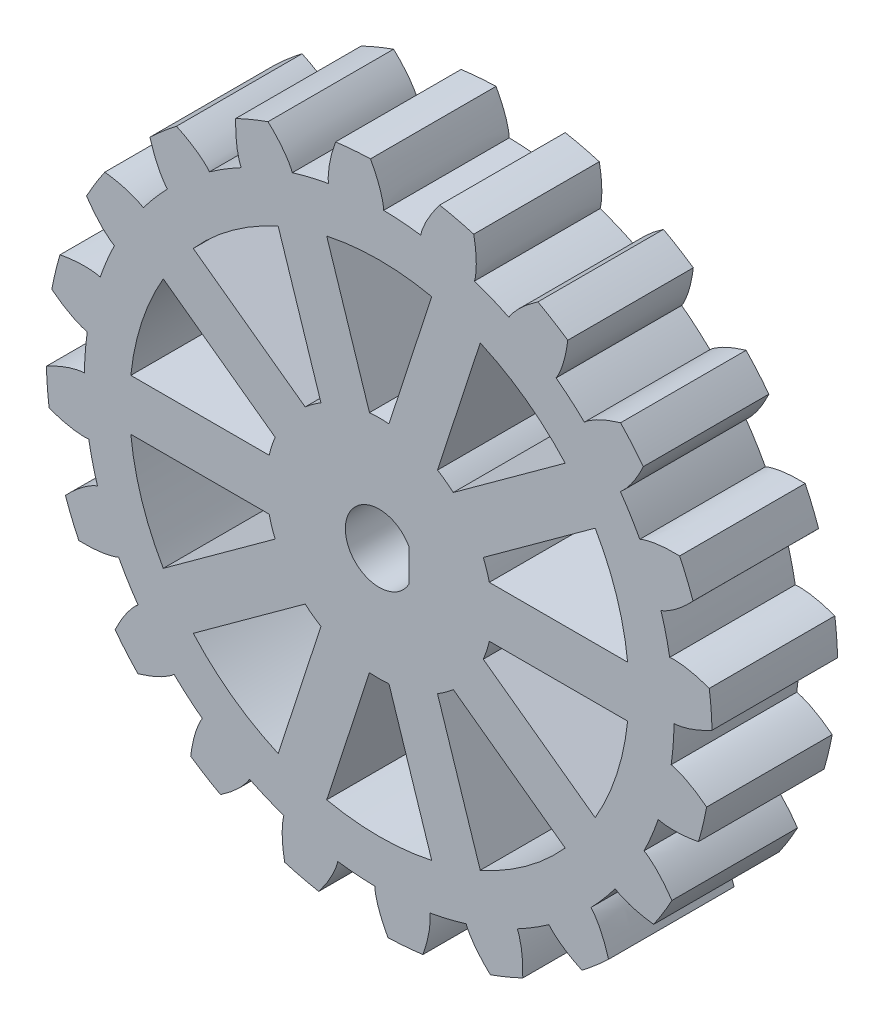
SolidWorks part; units mm, degrees
ref_plane "Front Plane" through (0, 0, 0) normal (0, 0, 1) x (1, 0, 0)
ref_plane "Top Plane" through (0, 0, 0) normal (0, 1, 0) x (1, 0, 0)
ref_plane "Right Plane" through (0, 0, 0) normal (1, 0, 0) x (0, 0, -1)
sketch "Sketch6" plane through (0, 0, 0) normal (0, 0, 1) x (1, 0, 0)
  line L0 (87.6899, 36.827) -> (87.6899, 90.4407) construction
  line L1 (87.6899, 61.8261) -> (62.7181, 61.8261) construction
  line L2 (87.6899, 61.8261) -> (56.3004, 50.4013) construction
  line L3 (79.6554, 58.9018) -> (87.6899, 61.8261) construction
  line L4 (77.8074, 58.1386) -> (87.3788, 62.5771) construction
  line L5 (76.0304, 57.2208) -> (86.9259, 63.45) construction
  line L6 (74.338, 56.1551) -> (86.3097, 64.4252) construction
  line L7 (81.5622, 59.5052) -> (87.8859, 61.2139) construction
  line L8 (83.5134, 59.9442) -> (87.9914, 60.7533) construction
  line L9 (85.4949, 60.2157) -> (88.0342, 60.454) construction
  line L10 (87.4923, 60.3177) -> (88.0428, 60.3223) construction
  line L11 (88.0428, 60.3223) -> (88.0425, 60.3158) construction
  line L12 (88.0425, 60.3158) -> (88.0425, 60.3094) construction
  line L13 (87.6899, 36.827) -> (85.2614, 67.5128) construction
  line L14 (111.173, 36.827) -> (112.6899, 36.827) construction
  line L15 (112.6899, 36.827) -> (114.2068, 36.827) construction
  circle A0 centre (87.6899, 36.827) radius 26.5169 construction
  circle A1 centre (87.6899, 36.827) radius 25 construction
  circle A2 centre (87.6899, 36.827) radius 23.4915 construction
  arc A3 (79.6554, 58.9018) -> (77.8074, 58.1386) centre (87.6899, 36.827) ccw construction
  arc A4 (77.8074, 58.1386) -> (76.0304, 57.2208) centre (87.6899, 36.827) ccw construction
  arc A5 (76.0304, 57.2208) -> (74.338, 56.1551) centre (87.6899, 36.827) ccw construction
  arc A6 (79.6554, 58.9018) -> (81.5622, 59.5052) centre (87.6899, 36.827) cw construction
  arc A7 (81.5622, 59.5052) -> (83.5134, 59.9442) centre (87.6899, 36.827) cw construction
  arc A8 (83.5134, 59.9442) -> (85.4949, 60.2157) centre (87.6899, 36.827) cw construction
  arc A9 (85.4949, 60.2157) -> (87.4923, 60.3177) centre (87.6899, 36.827) cw construction
  circle A10 centre (87.6899, 36.827) radius 23.485 construction
  spline S0 degree 3 poles (88.0425, 60.3094) (88.0393, 60.4586) (87.9965, 60.763) (87.8787, 61.2705) (87.6796, 61.8825) (87.2187, 62.9893) (86.7132, 63.8389) (86.3097, 64.4252) knots 0 0 0 0 0.099096 0.20382 0.346132 0.526411 1 1 1 1 construction
  spline S1 degree 3 poles (83.648, 59.9616) (83.6277, 60.1095) (83.6221, 60.4168) (83.6586, 60.9366) (83.759, 61.5723) (84.04, 62.7378) (84.4056, 63.6562) (84.7119, 64.2988) knots 0 0 0 0 0.099096 0.20382 0.346132 0.526411 1 1 1 1 construction
  point P7 (79.6554, 58.9018)
  dimension "D2" = 50
  dimension "D4" = 2
  dimension "D7" = 2
  dimension "D13" = 2
  dimension "D17" = 2
  dimension "D3" = 20
  dimension "D5" = 8.5502
  dimension "D6" = 10.5505
  dimension "D8" = 12.5505
  dimension "D9" = 2
  dimension "D10" = 14.5505
  dimension "D11" = 2
  dimension "D12" = 6.5505
  dimension "D14" = 4.5505
  dimension "D15" = 2
  dimension "D16" = 2.5505
  dimension "D18" = 0.5505
  dimension "D19" = 4.525
sketch "Sketch7" plane through (0, 0, 0) normal (0, 0, 1) x (1, 0, 0)
  circle A0 centre (87.6899, 36.827) radius 23.485 construction
  circle A1 centre (87.6899, 36.827) radius 26.5169 construction
  arc A2 (88.0425, 60.3094) -> (83.648, 59.9616) centre (87.6899, 36.827) ccw construction
  arc A3 (86.9912, 63.3347) -> (84.2104, 63.1146) centre (87.6899, 36.827) ccw construction
  spline S0 degree 3 poles (-1911.6865, 35.1483) (71.5756, 40.4372) (89.8382, 52.8293) (87.8787, 61.2705) (87.6796, 61.8825) (75.5402, 91.0375) (-65.3864, 59.6539) (2084.1552, 156.0334) knots -5.410264 -5.410264 -5.410264 -5.410264 0.099096 0.20382 0.346132 0.526411 21.176223 21.176223 21.176223 21.176223 only from (88.0425, 60.3094) to (86.3097, 64.4252) construction
  spline S1 degree 3 poles (2062.4411, 349.6638) (103.0357, 42.927) (83.0512, 52.2922) (83.6586, 60.9366) (83.759, 61.5723) (91.1612, 92.2738) (235.27, 83.4481) (-1902.673, -159.4872) knots -5.410264 -5.410264 -5.410264 -5.410264 0.099096 0.20382 0.346132 0.526411 21.176223 21.176223 21.176223 21.176223 only from (83.648, 59.9616) to (84.7119, 64.2988) construction
  spline S2 degree 3 poles (88.0425, 60.3094) (88.0393, 60.4586) (87.9965, 60.763) (87.8787, 61.2705) (87.6796, 61.8825) (87.3837, 62.5931) (87.1297, 63.087) (86.9912, 63.3347) knots 0 0 0 0 0.099096 0.20382 0.346132 0.526411 0.715001 0.715001 0.715001 0.715001 construction
  spline S3 degree 3 poles (83.648, 59.9616) (83.6277, 60.1095) (83.6221, 60.4168) (83.6586, 60.9366) (83.759, 61.5723) (83.9394, 62.3206) (84.1125, 62.8482) (84.2104, 63.1146) knots 0 0 0 0 0.099096 0.20382 0.346132 0.526411 0.715001 0.715001 0.715001 0.715001 construction
sketch "Sketch11" plane through (0, 0, 0) normal (0, 0, 1) x (1, 0, 0)
  circle A0 centre (0, 0) radius 23.485
  dimension "D1" = 46.97
extrude "Boss-Extrude6" add sketch "Sketch11" along normal blind 10
sketch "Sketch12" plane through (0, 0, 10) normal (0, 0, 1) x (1, 0, 0)
  arc A2 (-0.6987, 26.5077) -> (-3.4795, 26.2876) centre (0, 0) ccw
  arc A3 (0.3526, 23.4824) -> (-4.0419, 23.1346) centre (0, 0) ccw
  spline S2 degree 3 poles (-4.0419, 23.1346) (-4.0622, 23.2824) (-4.0678, 23.5897) (-4.0313, 24.1095) (-3.9309, 24.7452) (-3.7505, 25.4935) (-3.5774, 26.0212) (-3.4795, 26.2876) knots 0 0 0 0 0.099096 0.20382 0.346132 0.526411 0.715001 0.715001 0.715001 0.715001
  spline S3 degree 3 poles (0.3526, 23.4824) (0.3494, 23.6316) (0.3066, 23.9359) (0.1887, 24.4435) (-0.0104, 25.0555) (-0.3062, 25.7661) (-0.5602, 26.26) (-0.6987, 26.5077) knots 0 0 0 0 0.099096 0.20382 0.346132 0.526411 0.715001 0.715001 0.715001 0.715001
extrude "Boss-Extrude7" add sketch "Sketch12" against normal blind 10
pattern_circular "CirPattern2" count 20 over 360 about axis through (0, 0, 10) along (0, 0, 1) of "Boss-Extrude7"
sketch "Sketch13" plane through (0, 0, 10) normal (0, 0, 1) x (1, 0, 0)
  line L0 (2.45, 1.1347) -> (2.45, -1.1347)
  arc A0 (2.45, 1.1347) -> (2.45, -1.1347) centre (0, 0) ccw
  dimension "D1" = 5.4
  dimension "D2" = 2.45
extrude "Cut-Extrude2" cut sketch "Sketch13" against normal blind 10
sketch "Sketch14" plane through (0, 0, 0) normal (0, 0, -1) x (-1, 0, 0)
  line L1 (-7.3601, 2.8365) -> (-17.1995, 9.9851)
  line L2 (-7.6217, -2.0314) -> (-19.7838, -2.0314)
  line L4 (-7.6217, 2.0314) -> (-19.7838, 2.0314)
  line L8 (-4.972, 6.1234) -> (-14.8114, 13.2721)
  line L9 (-4.2873, 6.6209) -> (-8.0455, 18.1877)
  line L10 (-0.4232, 7.8764) -> (-4.1815, 19.4432)
  line L11 (0.4232, 7.8764) -> (4.1815, 19.4432)
  line L12 (4.2873, 6.6209) -> (8.0455, 18.1877)
  line L13 (4.972, 6.1234) -> (14.8114, 13.2721)
  line L14 (7.3601, 2.8365) -> (17.1995, 9.9851)
  line L15 (7.6217, 2.0314) -> (19.7838, 2.0314)
  line L16 (7.6217, -2.0314) -> (19.7838, -2.0314)
  line L17 (7.3601, -2.8365) -> (17.1995, -9.9851)
  line L18 (4.972, -6.1234) -> (14.8114, -13.2721)
  line L19 (4.2873, -6.6209) -> (8.0455, -18.1877)
  line L20 (0.4232, -7.8764) -> (4.1815, -19.4432)
  line L21 (-0.4232, -7.8764) -> (-4.1815, -19.4432)
  line L22 (-4.2873, -6.6209) -> (-8.0455, -18.1877)
  line L23 (-4.972, -6.1234) -> (-14.8114, -13.2721)
  line L24 (-7.3601, -2.8365) -> (-17.1995, -9.9851)
  circle A0 centre (0, 0) radius 19.8878 construction
  arc A1 (-4.1815, -19.4432) -> (4.1815, -19.4432) centre (0, 0) ccw
  circle A2 centre (0, 0) radius 22.8878 construction
  arc A3 (-0.4232, -7.8764) -> (0.4232, -7.8764) centre (0, 0) ccw
  circle A4 centre (0, 0) radius 7.8878 construction
  arc A5 (-4.972, -6.1234) -> (-4.2873, -6.6209) centre (0, 0) ccw
  arc A6 (-14.8114, -13.2721) -> (-8.0455, -18.1877) centre (0, 0) ccw
  arc A7 (4.2873, -6.6209) -> (4.972, -6.1234) centre (0, 0) ccw
  arc A8 (8.0455, -18.1877) -> (14.8114, -13.2721) centre (0, 0) ccw
  arc A9 (17.1995, -9.9851) -> (19.7838, -2.0314) centre (0, 0) ccw
  arc A10 (7.3601, -2.8365) -> (7.6217, -2.0314) centre (0, 0) ccw
  arc A11 (7.6217, 2.0314) -> (7.3601, 2.8365) centre (0, 0) ccw
  arc A12 (19.7838, 2.0314) -> (17.1995, 9.9851) centre (0, 0) ccw
  arc A13 (4.972, 6.1234) -> (4.2873, 6.6209) centre (0, 0) ccw
  arc A14 (14.8114, 13.2721) -> (8.0455, 18.1877) centre (0, 0) ccw
  arc A15 (0.4232, 7.8764) -> (-0.4232, 7.8764) centre (0, 0) ccw
  arc A16 (4.1815, 19.4432) -> (-4.1815, 19.4432) centre (0, 0) ccw
  arc A17 (-4.2873, 6.6209) -> (-4.972, 6.1234) centre (0, 0) ccw
  arc A18 (-8.0455, 18.1877) -> (-14.8114, 13.2721) centre (0, 0) ccw
  arc A19 (-7.3601, 2.8365) -> (-7.6217, 2.0314) centre (0, 0) ccw
  arc A20 (-17.1995, 9.9851) -> (-19.7838, 2.0314) centre (0, 0) ccw
  arc A21 (-19.7838, -2.0314) -> (-17.1995, -9.9851) centre (0, 0) ccw
  arc A22 (-7.6217, -2.0314) -> (-7.3601, -2.8365) centre (0, 0) ccw
  point P8 (-13.8878, 0)
  point P56 (0, 0)
  dimension "D1" = 3
  dimension "D2" = 12
  dimension "D3" = 10
extrude "Cut-Extrude3" cut sketch "Sketch14" against normal through all
sketch "Sketch16" plane through (0, 0, 0) normal (0, 0, -1) x (-1, 0, 0)
  line L0 (-2.45, -1.1347) -> (-2.45, 1.1347) construction
  line L1 (-2.45, -1.1347) -> (-2.45, 1.1347) construction
  line L2 (-2.375, 1.2843) -> (-2.375, -1.2843)
  arc A0 (-2.45, -1.1347) -> (-2.45, 1.1347) centre (0, 0) ccw construction
  arc A1 (-2.375, -1.2843) -> (-2.375, 1.2843) centre (0, 0) ccw
  circle A2 centre (0, 0) radius 9
  point P6 (0, 0)
  dimension "D1" = 18
  dimension "D2" = 0.15
extrude "Boss-Extrude9" add sketch "Sketch16" along normal blind 10 and the other way up to surface (10 mm away) other way up to face at (-13.0997, 4.2563, 10)
sketch "Sketch17" plane through (2.375, 0, 0) normal (-1, 0, 0) x (0, 0, 1)
  line L1 (-10, 1.2843) -> (-10, -1.2843) construction
  circle A0 centre (-5, 0) radius 1
  point P4 (0, 0)
  point P5 (0, 0)
  point P6 (-10, 0)
  dimension "D1" = 2
  dimension "D2" = 5
extrude "Cut-Extrude4" cut sketch "Sketch17" against normal blind 20
